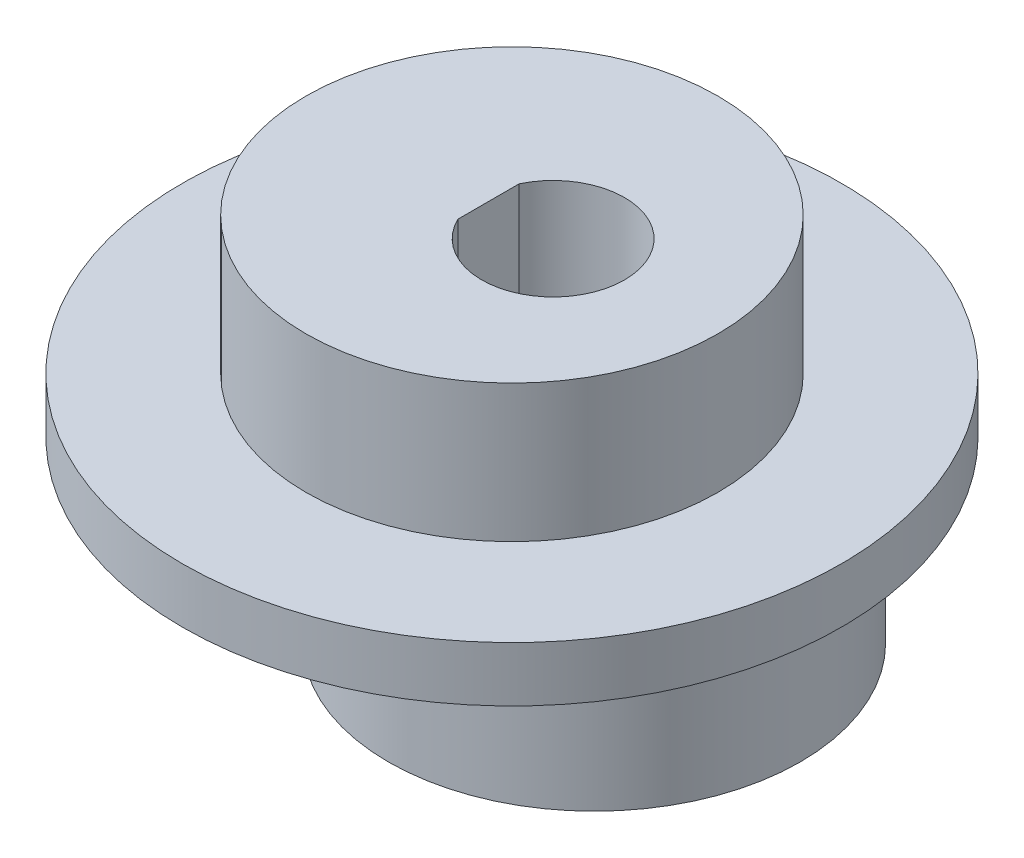
SolidWorks part; units mm, degrees
ref_plane "Front Plane" through (0, 0, 0) normal (0, 0, 1) x (1, 0, 0)
ref_plane "Top Plane" through (0, 0, 0) normal (0, 1, 0) x (1, 0, 0)
ref_plane "Right Plane" through (0, 0, 0) normal (1, 0, 0) x (0, 0, -1)
sketch "Sketch2" plane through (0, 0, 0) normal (0, 1, 0) x (1, 0, 0)
  line L0 (0, 0) -> (1.5, 0)
  circle A0 centre (0, 0) radius 12
  circle A1 centre (0, 0) radius 7.5
  dimension "D1" = 24
  dimension "D2" = 15
  dimension "D3" = 1.5
extrude "Boss-Extrude1" add sketch "Sketch2" along normal blind 5 contours A1 region at (-7.2879, 0, 0)
extrude "Boss-Extrude2" add sketch "Sketch2<3>" against normal blind 2 separate body contours A0 A1 region at (-11.6606, 0, 0)
sketch "Sketch2<3>" plane through (0, 0, 0) normal (0, 1, 0) x (1, 0, 0) same geometry as "Sketch2"
extrude "Boss-Extrude4" add sketch "Sketch2<5>" against normal blind 2 contours A1 region at (-7.2879, 0, 0)
sketch "Sketch2<5>" plane through (0, 0, 0) normal (0, 1, 0) x (1, 0, 0) same geometry as "Sketch2"
sketch "Sketch4" plane through (0, -2, 0) normal (0, -1, 0) x (1, 0, 0)
  line L0 (0, 0) -> (3, 0) construction
  circle A0 centre (3, 0) radius 7.5
  dimension "D2" = 15
  dimension "D1" = 3
extrude "Boss-Extrude5" add sketch "Sketch4" along normal blind 5
sketch "Sketch6" plane through (0, 5, 0) normal (0, 1, 0) x (1, 0, 0)
  line L0 (0, 0) -> (1.5, 0) construction
  line L1 (-0.85, -1.1124) -> (-0.85, 1.1124)
  arc A0 (-0.85, -1.1124) -> (-0.85, 1.1124) centre (1.5, 0) ccw
  point P8 (-0.85, 0)
  dimension "D2" = 5.2
  dimension "D1" = 1.5
extrude "Cut-Extrude1" cut sketch "Sketch6" against normal through all contours A0 L1
